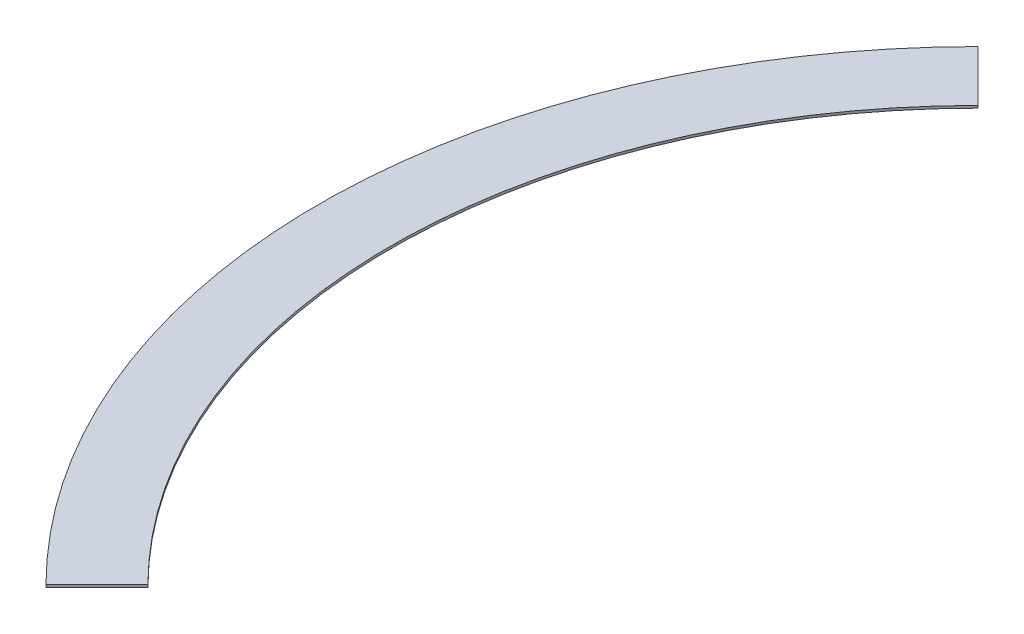
SolidWorks part; units mm, degrees
material "普通碳钢"
ref_plane "前视基准面" through (0, 0, 0) normal (0, 0, 1) x (1, 0, 0)
ref_plane "上视基准面" through (0, 0, 0) normal (0, 1, 0) x (1, 0, 0)
ref_plane "右视基准面" through (0, 0, 0) normal (1, 0, 0) x (0, 0, -1)
sketch "草图1" plane through (0, 0, 0) normal (0, 1, 0) x (1, 0, 0)
  line L0 (0, 0) -> (-1097.5, 0) construction
  line L1 (0, 0) -> (0, 1097.5) construction
  line L2 (0, 0) -> (-776.0497, 776.0497) construction
  line L3 (0, 0) -> (-776.0497, -776.0497) construction
  line L4 (-776.0497, 776.0497) -> (-691.1969, 691.1969)
  line L5 (-776.0497, -776.0497) -> (-691.1969, -691.1969)
  circle A0 centre (0, 0) radius 977.5 construction
  circle A1 centre (0, 0) radius 1097.5 construction
  arc A2 (-776.0497, -776.0497) -> (-776.0497, 776.0497) centre (0, 0) cw
  arc A3 (-691.1969, -691.1969) -> (-691.1969, 691.1969) centre (0, 0) cw
  dimension "D1" = 1955
  dimension "D2" = 2195
  dimension "D3" = 45
  dimension "D4" = 45
base flange "基体-法兰1" sketch "草图1" thickness 4 reverse thickness direction no parameters "D1"=4
sketch "草图6" plane through (0, 0, 0) normal (0, 1, 0) x (1, 0, 0)
  line L1 (-1097.5, 776.0497) -> (-691.1969, 776.0497)
  line L2 (-1097.5, 776.0497) -> (-1097.5, -776.0497)
  line L3 (-1097.5, -776.0497) -> (-691.1969, -776.0497)
  line L4 (-691.1969, 776.0497) -> (-691.1969, -776.0497)
  arc A0 (-776.0497, 776.0497) -> (-776.0497, -776.0497) centre (0, 0) ccw construction
  dimension "D1" = 406.3031
  dimension "D2" = 1552.0994
sketch "折弯-线1" plane through (0, 0, 0) normal (0, 1, 0) x (1, 0, 0)
sketch "边界框1" plane through (0, 0, 0) normal (0, 1, 0) x (1, 0, 0)
sheet metal parameters "钣金2" thickness 4 parameters "D1"=4
flat pattern "平板型式2" [suppressed]
sketch "折弯-线2" plane through (0, 0, 0) normal (0, 1, 0) x (1, 0, 0)
sketch "边界框2" [suppressed] plane through (0, 0, 0) normal (0, 1, 0) x (1, 0, 0)
